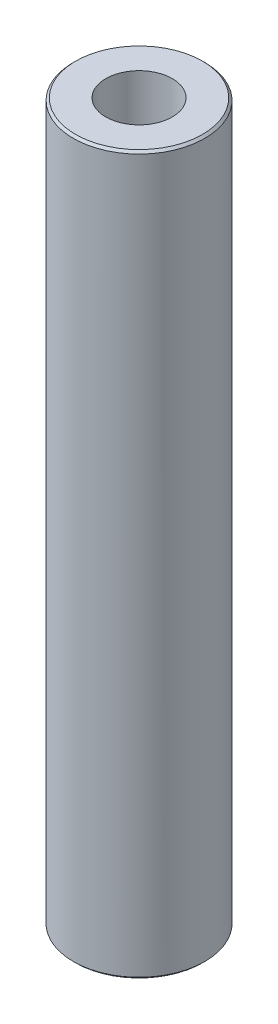
SolidWorks part; units mm, degrees
ref_plane "Front Plane" through (0, 0, 0) normal (0, 0, 1) x (1, 0, 0)
ref_plane "Top Plane" through (0, 0, 0) normal (0, 1, 0) x (1, 0, 0)
ref_plane "Right Plane" through (0, 0, 0) normal (1, 0, 0) x (0, 0, -1)
sketch "Sketch1" plane through (0, 0, 0) normal (0, 1, 0) x (1, 0, 0)
  circle A0 centre (0, 0) radius 55
  dimension "SHAFT_OD" = 110
extrude "Boss-Extrude1" add sketch "Sketch1" along normal blind 600
sketch "Sketch2" plane through (0, 0, 0) normal (0, 1, 0) x (1, 0, 0)
  circle A0 centre (0, 0) radius 27.816
  dimension "BORE_D" = 55.6319
extrude "Cut-Extrude1" cut sketch "Sketch2" along normal through all
chamfer "Chamfer1" distance 1.9056 angle 45 2 edges at (0, 600, 55) (0, 0, 55)
